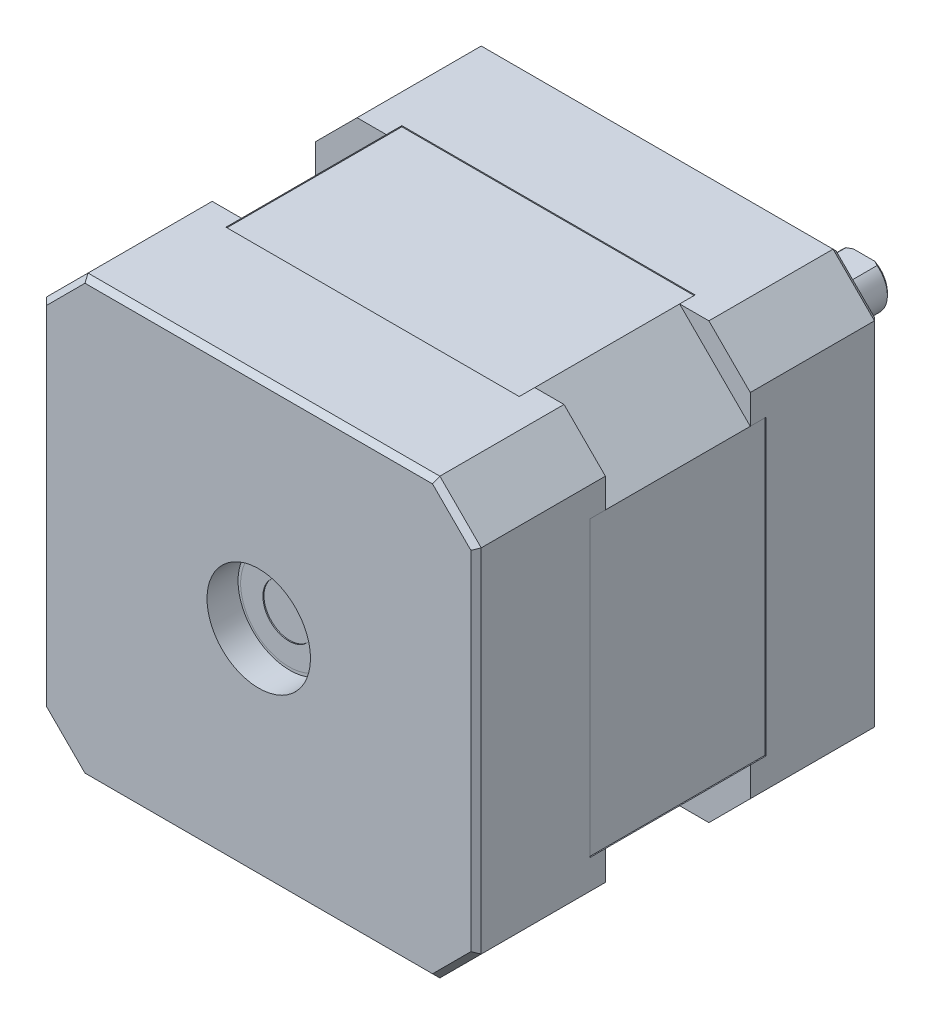
SolidWorks part; units mm, degrees
ref_plane "Alzado" through (0, 0, 0) normal (0, 0, 1) x (1, 0, 0)
ref_plane "Planta" through (0, 0, 0) normal (0, 1, 0) x (1, 0, 0)
ref_plane "Vista lateral" through (0, 0, 0) normal (1, 0, 0) x (0, 0, -1)
sketch "Croquis1" plane through (0, 0, 0) normal (0, 0, 1) x (1, 0, 0)
  line L1 (-21, 21) -> (21, 21)
  line L2 (-21, 21) -> (-21, -21)
  line L3 (-21, -21) -> (21, -21)
  line L4 (21, 21) -> (21, -21)
  line L5 (-21, 21) -> (21, -21) construction
  line L6 (-21, -21) -> (21, 21) construction
  point P0 (0, 0)
extrude "Saliente-Extruir1" add sketch "Croquis1" along normal blind 39
chamfer "Chaflán2" distance 4 angle 45 4 edges at (21, -21, 19.5) (21, 21, 19.5) (-21, 21, 19.5) (-21, -21, 19.5)
chamfer "Chaflán3" distance 0.5 angle 45 16 edges at (-19, -19, 39) (-21, 0, 39) (-19, 19, 39) (0, 21, 39) (19, 19, 39) (21, 0, 39) (19, -19, 39) (0, -21, 39) (19, 19, 0) (0, 21, 0) (-19, 19, 0) (-21, 0, 0) (-19, -19, 0) (0, -21, 0) (19, -19, 0) (21, 0, 0)
sketch "Croquis2" plane through (0, 0, 0) normal (0, 0, -1) x (-1, 0, 0)
  circle A0 centre (0, 0) radius 15
extrude "Cortar-Extruir2" cut sketch "Croquis2" against normal blind 0.5
chamfer "Chaflán4" distance 1 angle 45 1 edges at (-15, 0, 0.5)
sketch "Croquis3" plane through (0, 0, 0.5) normal (0, 0, -1) x (-1, 0, 0)
  circle A0 centre (0, 0) radius 11
  circle A1 centre (0, 0) radius 4.75
extrude "Saliente-Extruir2" add sketch "Croquis3" along normal blind 2.5
sketch "Croquis4" plane through (0, 0, 0.5) normal (0, 0, -1) x (-1, 0, 0)
  circle A0 centre (0, 0) radius 2.5
extrude "Saliente-Extruir3" add sketch "Croquis4" along normal blind 20
chamfer "Chaflán5" distance 0.25 angle 45 1 edges at (-2.5, 0, -19.5)
sketch "Croquis5" plane through (0, 0, -19.5) normal (0, 0, -1) x (-1, 0, 0)
  line L1 (-18.1031, 12.3221) -> (8.4507, 12.3221)
  line L2 (-18.1031, 12.3221) -> (-18.1031, 2)
  line L3 (-18.1031, 2) -> (8.4507, 2)
  line L4 (8.4507, 12.3221) -> (8.4507, 2)
  line L5 (-18.1031, 12.3221) -> (8.4507, 2) construction
  line L6 (-18.1031, 2) -> (8.4507, 12.3221) construction
  point P0 (-4.8262, 7.161)
  dimension "D1" = 2
extrude "Cortar-Extruir3" cut sketch "Croquis5" against normal up to surface (17.5 mm away) up to face at (-11, 0, -2)
sketch "Croquis6" plane through (0, 0, 0) normal (0, 0, -1) x (-1, 0, 0)
  line L1 (-21, -17) -> (-21, 17) construction
  line L2 (-17, 21) -> (17, 21) construction
  circle A0 centre (-15.35, 15.35) radius 1.5
  dimension "D1" = 5.65
  dimension "D2" = 5.65
extrude "Cortar-Extruir4" cut sketch "Croquis6" against normal blind 12
pattern_circular "MatrizC1" count 4 over 360 about axis through (0, 0, -19.5) along (0, 0, 1) of "Cortar-Extruir4"
sketch "Croquis7" plane through (-19, -19, 0) normal (-0.7071, -0.7071, 0) x (0, 0, 1)
  line L0 (0, -2.6213) -> (0, 2.6213) construction
  line L1 (12.5, -8.4668) -> (26.5, -8.4668)
  line L2 (12.5, -8.4668) -> (12.5, 8.4668)
  line L3 (12.5, 8.4668) -> (26.5, 8.4668)
  line L4 (26.5, -8.4668) -> (26.5, 8.4668)
  line L5 (12.5, -8.4668) -> (26.5, 8.4668) construction
  line L6 (12.5, 8.4668) -> (26.5, -8.4668) construction
  point P0 (19.5, 0)
  dimension "D1" = 14
  dimension "D2" = 19.5
extrude "Cortar-Extruir5" cut sketch "Croquis7" against normal blind 2
pattern_circular "MatrizC2" count 4 over 360 about axis through (0, 0, -19.5) along (0, 0, 1) of "Cortar-Extruir5"
sketch "Croquis8" plane through (0, 21, 0) normal (0, 1, 0) x (1, 0, 0)
  line L0 (-14.1716, -12.5) -> (-14.1716, -26.5)
  line L1 (14.1716, -12.5) -> (14.1716, -26.5)
  line L2 (-14.1716, -12.5) -> (-14.1716, -11)
  line L3 (-14.1716, -11) -> (14.1716, -11)
  line L4 (14.1716, -12.5) -> (14.1716, -11)
  line L6 (-14.1716, -26.5) -> (-14.1716, -28)
  line L7 (-14.1716, -28) -> (14.1716, -28)
  line L8 (14.1716, -26.5) -> (14.1716, -28)
extrude "Cortar-Extruir6" cut sketch "Croquis8" against normal blind 0.1
pattern_circular "MatrizC3" count 4 over 360 about axis through (0, 0, -19.5) along (0, 0, 1) of "Cortar-Extruir6"
sketch "Croquis9" plane through (0, 0, 39) normal (0, 0, 1) x (1, 0, 0)
  circle A0 centre (0, 0) radius 5
extrude "Cortar-Extruir7" cut sketch "Croquis9" against normal blind 3
sketch "Croquis10" plane through (0, 0, 36) normal (0, 0, 1) x (1, 0, 0)
  circle A0 centre (0, 0) radius 4.65
  circle A1 centre (0, 0) radius 2.5
extrude "Saliente-Extruir4" add sketch "Croquis10" along normal blind 0.1
